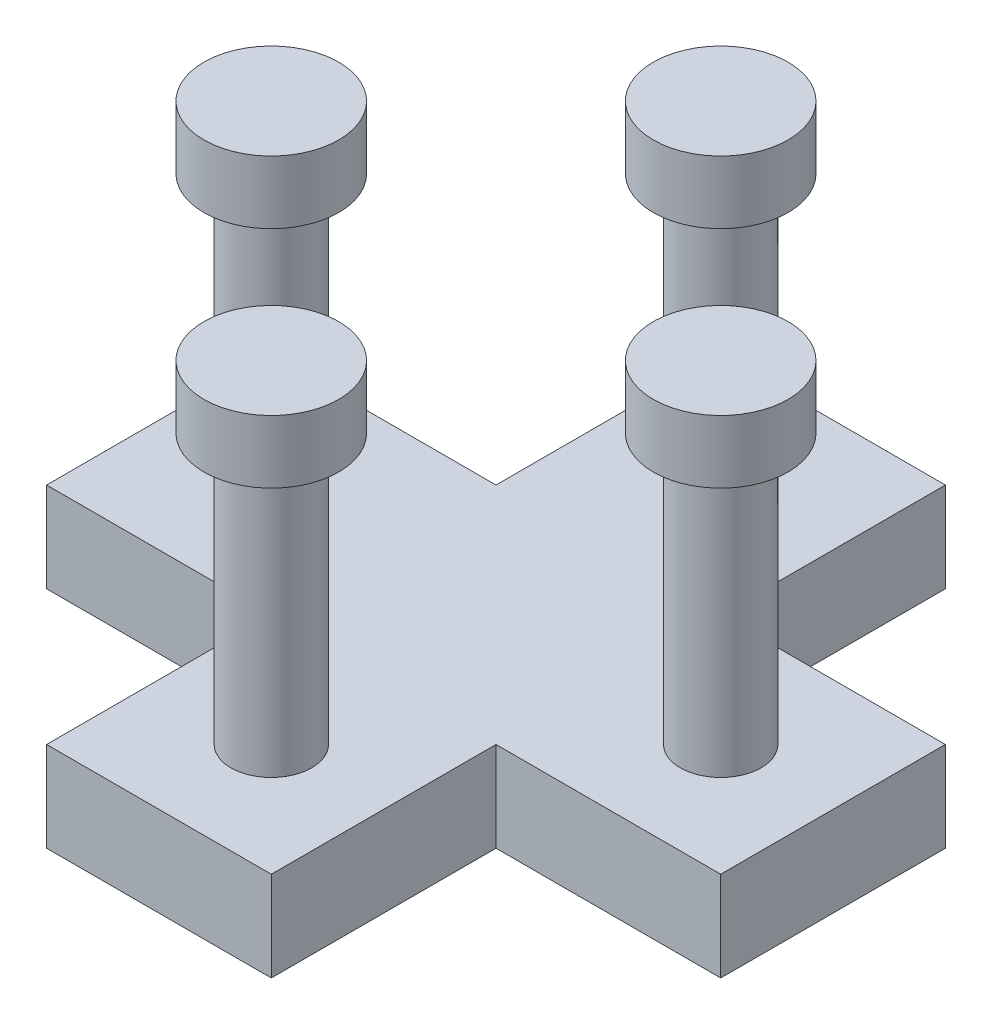
SolidWorks part; units mm, degrees
ref_plane "Front Plane" through (0, 0, 0) normal (0, 0, 1) x (1, 0, 0)
ref_plane "Top Plane" through (0, 0, 0) normal (0, 1, 0) x (1, 0, 0)
ref_plane "Right Plane" through (0, 0, 0) normal (1, 0, 0) x (0, 0, -1)
sketch "Sketch1" plane through (0, 0, 0) normal (0, 1, 0) x (1, 0, 0)
  line L0 (-8.3487, -10.4521) -> (-8.3487, -4.1021)
  line L1 (-8.3487, -4.1021) -> (-1.9987, -4.1021)
  line L2 (-1.9987, -4.1021) -> (-1.9987, -10.4521)
  line L3 (-1.9987, -10.4521) -> (4.3513, -10.4521)
  line L4 (4.3513, -10.4521) -> (4.3513, -16.8021)
  line L5 (4.3513, -16.8021) -> (-1.9987, -16.8021)
  line L6 (-1.9987, -16.8021) -> (-1.9987, -23.1521)
  line L7 (-1.9987, -23.1521) -> (-8.3487, -23.1521)
  line L8 (-8.3487, -23.1521) -> (-8.3487, -16.8021)
  line L9 (-8.3487, -16.8021) -> (-14.6987, -16.8021)
  line L10 (-14.6987, -16.8021) -> (-14.6987, -10.4521)
  line L11 (-14.6987, -10.4521) -> (-8.3487, -10.4521)
  dimension "D1" = 6.35
  dimension "D2" = 6.35
  dimension "D3" = 6.35
  dimension "D4" = 6.35
  dimension "D5" = 6.35
  dimension "D6" = 6.35
  dimension "D7" = 6.35
  dimension "D8" = 6.35
  dimension "D9" = 6.35
  dimension "D10" = 6.35
extrude "body" add sketch "Sketch1" along normal blind 2.54
sketch "Sketch2" plane through (0, 2.54, 0) normal (0, 1, 0) x (1, 0, 0)
  line L0 (-8.3487, -10.4521) -> (-14.6987, -10.4521) construction
  line L1 (-1.9987, -23.1521) -> (-1.9987, -16.8021) construction
  line L2 (-1.9987, -16.8021) -> (4.3513, -16.8021) construction
  line L3 (-1.9987, -10.4521) -> (-1.9987, -4.1021) construction
  line L4 (-1.9987, -4.1021) -> (-8.3487, -4.1021) construction
  line L5 (-14.6987, -10.4521) -> (-14.6987, -16.8021) construction
  line L6 (-8.3487, -23.1521) -> (-1.9987, -23.1521) construction
  line L7 (4.3513, -16.8021) -> (4.3513, -10.4521) construction
  circle A0 centre (-5.1737, -7.2771) radius 1.143
  circle A1 centre (1.1763, -13.6271) radius 1.143
  circle A2 centre (-5.1737, -19.9771) radius 1.143
  circle A3 centre (-11.5237, -13.6271) radius 1.143
  dimension "D1" = 2.286
  dimension "D2" = 2.286
  dimension "D3" = 2.286
  dimension "D4" = 2.286
  dimension "D5" = 3.175
  dimension "D6" = 3.175
  dimension "D7" = 3.175
  dimension "D8" = 3.175
  dimension "D9" = 3.175
  dimension "D10" = 3.175
  dimension "D11" = 3.175
  dimension "D12" = 3.175
extrude "pegs" add sketch "Sketch2" along normal blind 7.62
ref_point "centre 1"
ref_point "centre 2"
ref_point "centre 3"
ref_point "centre 4"
ref_plane "plane o' feet" through (0, 10.16, 0) normal (0, 1, 0) x (1, 0, 0)
sketch "Sketch3" plane through (0, 10.16, 0) normal (0, 1, 0) x (1, 0, 0)
  circle A0 centre (-5.1737, -7.2771) radius 1.905
  circle A1 centre (-11.5237, -13.6271) radius 1.905
  circle A2 centre (-5.1737, -19.9771) radius 1.905
  circle A3 centre (1.1763, -13.6271) radius 1.905
  dimension "D1" = 3.81
  dimension "D2" = 3.81
  dimension "D3" = 3.81
  dimension "D4" = 3.81
extrude "feet" add sketch "Sketch3" along normal blind 1.778
